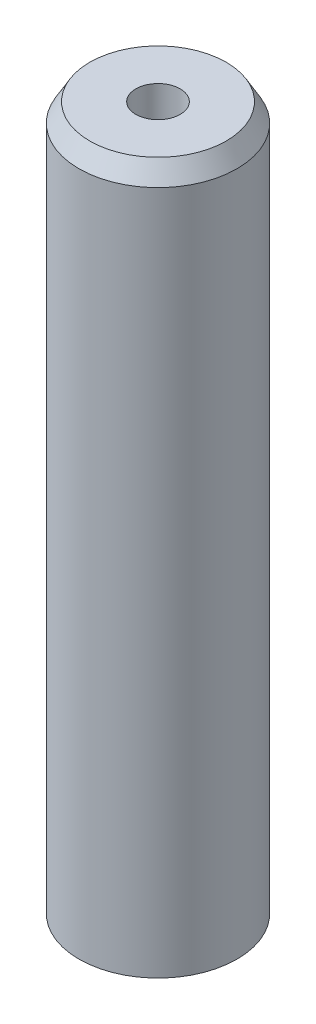
SolidWorks part; units mm, degrees
ref_plane "Front Plane" through (0, 0, 0) normal (0, 0, 1) x (1, 0, 0)
ref_plane "Top Plane" through (0, 0, 0) normal (0, 1, 0) x (1, 0, 0)
ref_plane "Right Plane" through (0, 0, 0) normal (1, 0, 0) x (0, 0, -1)
sketch "Sketch1" plane through (0, 0, 0) normal (0, 1, 0) x (1, 0, 0)
  circle A0 centre (0, 0) radius 10
  dimension "SHAFT_OD" = 20
extrude "Boss-Extrude1" add sketch "Sketch1" along normal blind 90.3687
sketch "Sketch2" plane through (0, 0, 0) normal (0, 1, 0) x (1, 0, 0)
  circle A0 centre (0, 0) radius 2.8069
  dimension "BORE_D" = 5.6139
extrude "Cut-Extrude1" cut sketch "Sketch2" along normal through all
chamfer "Chamfer1" distance 2.3603 angle 30 2 edges at (0, 90.3687, 10) (0, 0, 10) first distance on face at (0, 90.3687, 10) first distance on face at (0, 0, 2.8069)
